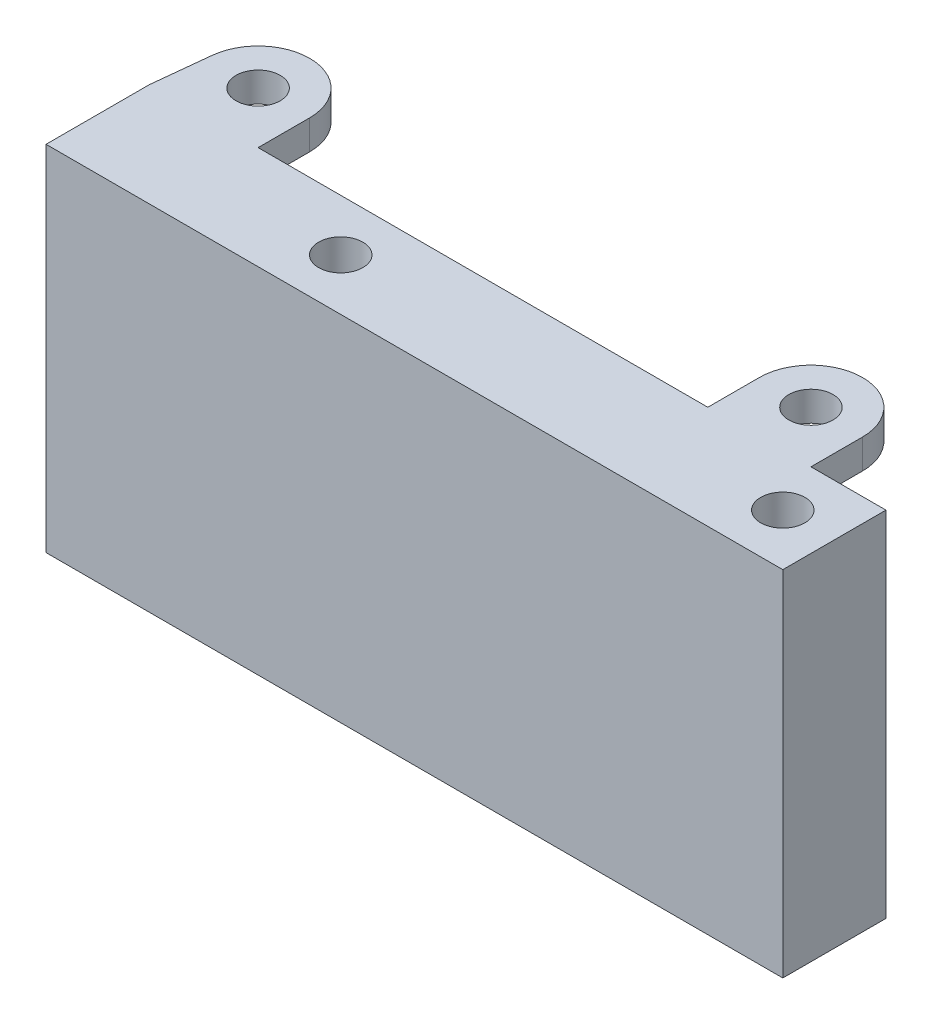
SolidWorks part; units mm, degrees
ref_plane "Front Plane" through (0, 0, 0) normal (0, 0, 1) x (1, 0, 0)
ref_plane "Top Plane" through (0, 0, 0) normal (0, 1, 0) x (1, 0, 0)
ref_plane "Right Plane" through (0, 0, 0) normal (1, 0, 0) x (0, 0, -1)
sketch "Sketch2" plane through (0, 0, 0) normal (0, 0, 1) x (1, 0, 0)
  line L0 (0, 0) -> (50, 0)
  line L1 (50, 0) -> (50, 24)
  line L2 (50, 24) -> (0, 24)
  line L3 (0, 24) -> (0, 0)
  dimension "D1" = 24
  dimension "D2" = 50
extrude "Boss-Extrude1" add sketch "Sketch2" along normal blind 7
sketch "Sketch3" plane through (0, 0, 0) normal (0, -1, 0) x (1, 0, 0)
  line L0 (7.3915, -3.5) -> (7.3915, 0)
  line L1 (0, 0) -> (50, 0) construction
  line L2 (7.3915, 0) -> (0, 0)
  line L3 (0, 0) -> (0.4111, -3.8698)
  line L4 (44.9101, -3.5) -> (44.9101, 0)
  line L5 (44.9101, 0) -> (37.9101, 0)
  line L6 (37.9101, 0) -> (37.9101, -3.5)
  line L7 (0, 7) -> (0, 0) construction
  circle A0 centre (41.4101, -3.5) radius 1.5 construction
  circle A1 centre (3.8915, -3.5) radius 1.5 construction
  circle A2 centre (41.4101, -3.5) radius 1.5
  circle A3 centre (3.8915, -3.5) radius 1.5
  arc A4 (0.4111, -3.8698) -> (7.3915, -3.5) centre (3.8915, -3.5) ccw
  arc A5 (37.9101, -3.5) -> (44.9101, -3.5) centre (41.4101, -3.5) ccw
  circle A6 centre (3.8915, -3.5) radius 3.5 construction
  circle A8 centre (41.4101, -3.5) radius 3.5 construction
  point P7 (44.4275, -3.75)
  point P12 (8.1192, -3.75)
  point P17 (0.7445, -0.8729)
  point P23 (0, 0)
  dimension "D1" = 2
  dimension "D2" = 2
extrude "Boss-Extrude2" add sketch "Sketch3" against normal blind 2
extrude "Boss-Extrude3" add sketch "Sketch3<2>" along normal blind 2 from surface starting at face at (25, 24, 3.5)
sketch "Sketch3<2>" plane through (0, 0, 0) normal (0, -1, 0) x (1, 0, 0) same geometry as "Sketch3"
sketch "Sketch5" plane through (0, 0, 0) normal (0, -1, 0) x (1, 0, 0)
  line L0 (0, 7) -> (50, 7) construction
  line L1 (50, 7) -> (50, 0) construction
  circle A0 centre (46.5, 3.5) radius 1.5
  circle A1 centre (46.5, 3.5) radius 3.5 construction
  dimension "D1" = 3
  dimension "D2" = 2
extrude "Cut-Extrude1" cut sketch "Sketch5" against normal up to surface (24 mm away) up to face at (25.5464, 24, -0.6527)
sketch "Sketch6" plane through (0, 0, 0) normal (0, -1, 0) x (1, 0, 0)
  line L0 (0, 7) -> (50, 7) construction
  line L1 (20, 10.2501) -> (20, 11.5862) construction
  circle A0 centre (16.5, 3.5) radius 1.5
  circle A1 centre (16.5, 3.5) radius 3.5 construction
  dimension "D1" = 2
  dimension "D2" = 3
extrude "Cut-Extrude2" cut sketch "Sketch6" against normal up to surface (24 mm away) up to face at (48, 24, 3.5)
